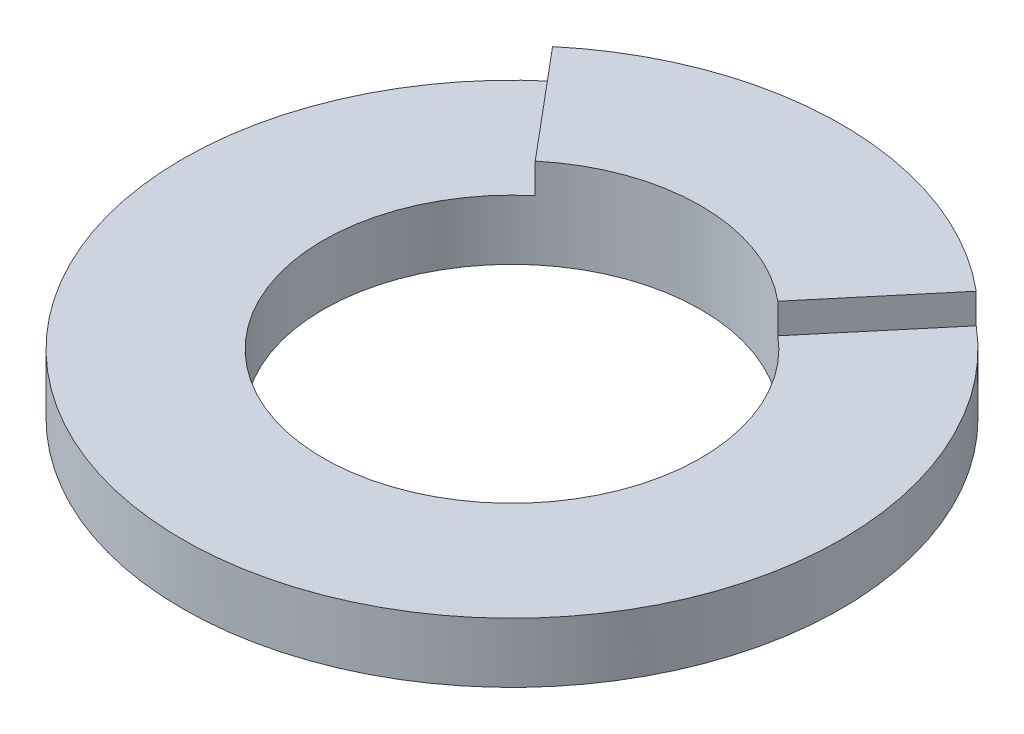
SolidWorks part; units mm, degrees
material "i190"
ref_plane "Front Plane" through (0, 0, 0) normal (0, 0, 1) x (1, 0, 0)
ref_plane "Top Plane" through (0, 0, 0) normal (0, 1, 0) x (1, 0, 0)
ref_plane "Right Plane" through (0, 0, 0) normal (1, 0, 0) x (0, 0, -1)
sketch "Sketch1" plane through (0, 0, 0) normal (0, 1, 0) x (1, 0, 0)
  circle A0 centre (0, 0) radius 5.5
  circle A1 centre (0, 0) radius 3.15
  dimension "D1" = 11
  dimension "D2" = 6.3
extrude "Boss-Extrude1" add sketch "Sketch1" along normal blind 1
sketch "Sketch2" plane through (0, 1, 0) normal (0, 1, 0) x (1, 0, 0)
  line L0 (-3.5357, 4.2129) -> (3.5357, 4.2129) construction
  line L1 (3.5357, 4.2129) -> (2.025, 2.4129)
  line L2 (-2.025, 2.4129) -> (-3.5357, 4.2129)
  line L3 (-2.025, 2.4129) -> (0, 0) construction
  line L4 (0, 0) -> (2.025, 2.4129) construction
  circle A0 centre (0, 0) radius 5.5 construction
  circle A1 centre (0, 0) radius 3.15 construction
  arc A2 (3.5357, 4.2129) -> (-3.5357, 4.2129) centre (0, 0) ccw
  arc A3 (2.025, 2.4129) -> (-2.025, 2.4129) centre (0, 0) ccw
  point P4 (0, 0)
  dimension "D1" = 4.05
extrude "Boss-Extrude2" add sketch "Sketch2" along normal blind 0.5
